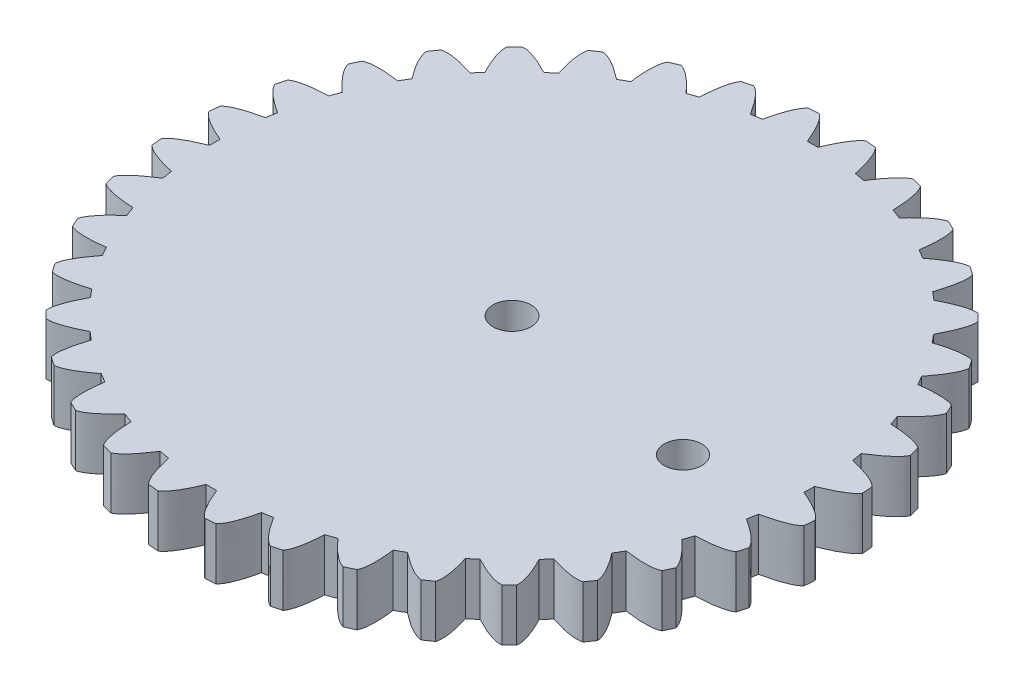
SolidWorks part; units mm, degrees
material "ABS"
ref_plane "Front Plane" through (0, 0, 0) normal (0, 0, 1) x (1, 0, 0)
ref_plane "Top Plane" through (0, 0, 0) normal (0, 1, 0) x (1, 0, 0)
ref_plane "Right Plane" through (0, 0, 0) normal (1, 0, 0) x (0, 0, -1)
sketch "Sketch1" plane through (0, 0, 0) normal (0, 1, 0) x (1, 0, 0)
  line L0 (18.9186, 21.5125) -> (21.7285, 18.6702) construction
  line L2 (20.3236, 20.0913) -> (22.457, 22.2004) construction
  line L3 (22.457, 22.2004) -> (22.5965, 22.3383)
  circle A0 centre (0, 0) radius 28.6479
  circle A1 centre (0, 0) radius 31.5781
  spline S0 degree 2 poles (21.7285, 18.6702) (24.8695, 24.5853) (18.9186, 21.5125) knots 0 0 0 1 1 1
  point P3 (18.9186, 21.5125)
  point P4 (21.7285, 18.6702)
  point P6 (22.1027, 22.5532)
  point P12 (18.1563, 22.1596)
  point P14 (22.5965, 22.3383)
  point P15 (22.8057, 21.842)
  point P16 (12.1095, 25.9627)
  dimension "D1" = 57.2958
  dimension "D4" = 3
  dimension "D5" = 1
  dimension "D2" = 4
  dimension "D3" = 1
extrude "Boss-Extrude4" add sketch "Sketch1" along normal blind 5 contours A0 | A0 S0 A1 region at (21.2325, 0, -20.9899) region at (0, 0, 0)
pattern_circular "CirPattern6" count 36 every 10 about axis through (0, 5, 0) along (0, 1, 0) of "Boss-Extrude4"
sketch "Sketch2" plane through (0, 5, 0) normal (0, 1, 0) x (1, 0, 0)
  circle A0 centre (0, 0) radius 1.825
  dimension "D1" = 3.65
extrude "Cut-Extrude2" cut sketch "Sketch2" against normal blind 10 contours A0 region at (0, 5, 0)
sketch "Sketch4" plane through (0, 0, 0) normal (0, -1, 0) x (1, 0, 0)
  circle A0 centre (19.7203, 3.3331) radius 1.8
  dimension "D1" = 20
  dimension "D2" = 3.6
extrude "Cut-Extrude3" cut sketch "Sketch4" against normal blind 10
equation "\"number-of-teeth\"= 36"
equation "\"gear-size\"= 4mm"
equation "\"circumference\"= \"number-of-teeth\" * ( ( 1 + \"space-between-teeth\" ) * \"gear-size\" )"
equation "\"space-between-teeth\"= .25"
equation "\"D1@Sketch1\" = \"circumference\" / pi"
equation "\"D2@Sketch1\"=\"gear-size\""
equation "\"gear-length\"= 3mm"
equation "\"D4@Sketch1\"=\"gear-length\""
equation "\"D5@Sketch1\"=\"gear-size\" * \"space-between-teeth\""
equation "\"D3@Sketch1\"=\"gear-size\" * \"space-between-teeth\""
equation "\"D1@CirPattern6\"=\"number-of-teeth\""
equation "\"D2@CirPattern6\"=360 / \"number-of-teeth\""
